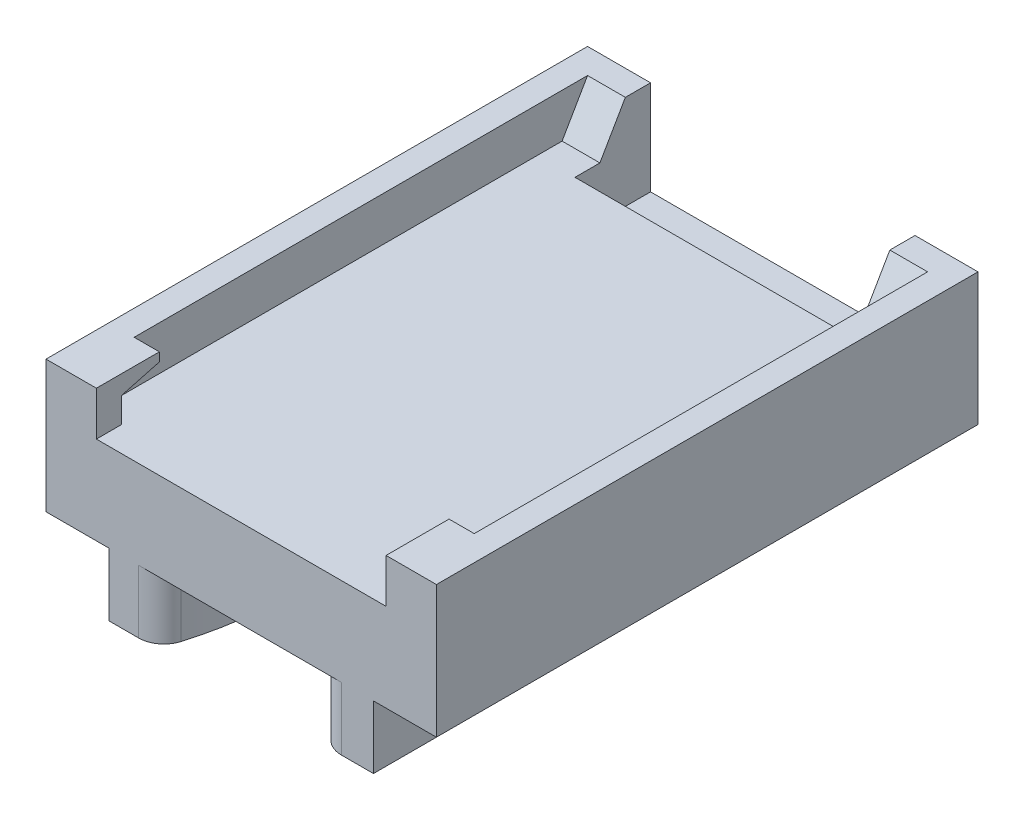
SolidWorks part; units mm, degrees
ref_plane "Płaszczyzna przednia" through (0, 0, 0) normal (0, 0, 1) x (1, 0, 0)
ref_plane "Płaszczyzna górna" through (0, 0, 0) normal (0, 1, 0) x (1, 0, 0)
ref_plane "Płaszczyzna prawa" through (0, 0, 0) normal (1, 0, 0) x (0, 0, -1)
sketch "Szkic1" plane through (0, 0, 0) normal (0, 1, 0) x (1, 0, 0)
  line L1 (-15.5, -21.5) -> (15.5, -21.5)
  line L2 (-15.5, -21.5) -> (-15.5, 21.5)
  line L3 (-15.5, 21.5) -> (15.5, 21.5)
  line L4 (15.5, -21.5) -> (15.5, 21.5)
  line L5 (-15.5, -21.5) -> (15.5, 21.5) construction
  line L6 (-15.5, 21.5) -> (15.5, -21.5) construction
  point P0 (0, 0)
  dimension "D1" = 31
  dimension "D2" = 43
extrude "Dodanie-wyciągnięcie1" add sketch "Szkic1" along normal blind 12
sketch "Szkic3" plane through (0, 0, 0) normal (0, -1, 0) x (1, 0, 0)
  line L19 (-10.2123, 28.1123) -> (-14.1254, 33.4595)
  line L21 (-10.2791, 46.0939) -> (-15.166, 51.1544)
  line L23 (-8.0445, 58.0315) -> (-4.2245, 54.0758)
  line L25 (5.1078, 53.9128) -> (9.0636, 57.7328)
  line L27 (15.9406, 50.6112) -> (10.88, 45.7243)
  line L29 (4.5535, 10.4212) -> (7.1435, -58.109)
  line L31 (6.5359, -61.1346) -> (1.3149, -72.3946)
  line L33 (-3.1199, -71.9285) -> (-5.8858, -59.8291)
  line L35 (-6.0512, -58.271) -> (-5.1193, 12.1724)
  arc A41 (-5.1193, 12.1724) -> (-10.2123, 28.1123) centre (-31.517, 12.5216) ccw
  arc A43 (-12.7415, 37.3422) -> (-14.1254, 33.4595) centre (-12.1147, 34.9308) ccw
  arc A45 (-12.7415, 37.3422) -> (-10.2791, 46.0939) centre (-14.0658, 42.4371) ccw
  arc A47 (-15.7507, 53.061) -> (-15.166, 51.1544) centre (-13.5835, 52.6827) ccw
  arc A49 (-10.429, 58.552) -> (-15.7507, 53.061) centre (-7.0711, 49.9733) ccw
  arc A51 (-8.0445, 58.0315) -> (-10.429, 58.552) centre (-9.6271, 56.5033) ccw
  arc A53 (-4.2245, 54.0758) -> (5.1078, 53.9128) centre (0.5231, 58.6605) ccw
  arc A55 (10.9702, 58.3174) -> (9.0636, 57.7328) centre (10.5918, 56.1502) ccw
  arc A57 (14.1036, 56.4511) -> (10.9702, 58.3174) centre (8.485, 50.5815) ccw
  arc A59 (16.4611, 52.9956) -> (14.1036, 56.4511) centre (7.7554, 49.5882) ccw
  arc A61 (15.9406, 50.6112) -> (16.4611, 52.9956) centre (14.4124, 52.1938) ccw
  arc A63 (10.88, 45.7243) -> (10.8712, 38.1593) centre (14.5367, 41.9376) ccw
  arc A65 (10.8712, 38.1593) -> (12.249, 37.1965) centre (14.5366, 41.9375) ccw
  arc A67 (13.9716, 36.3736) -> (12.249, 37.1965) centre (10.996, 32.3591) ccw
  arc A69 (14.2827, 32.9633) -> (13.9716, 36.3736) centre (12.3247, 34.504) ccw
  arc A71 (14.2827, 32.9633) -> (5.8286, 19.5982) centre (47.6073, 2.5276) ccw
  arc A73 (5.8286, 19.5982) -> (4.5535, 10.4212) centre (31.0167, 11.4214) ccw
  arc A75 (6.5359, -61.1346) -> (7.1435, -58.109) centre (0.5482, -58.3583) ccw
  arc A77 (-3.1199, -71.9285) -> (1.3149, -72.3946) centre (-0.8228, -71.4034) ccw
  arc A79 (-6.0512, -58.271) -> (-5.8858, -59.8291) centre (0.5482, -58.3583) ccw
extrude "Dodanie-wyciągnięcie3" add sketch "Szkic3" against normal offset from surface (5 mm away) 7 separate body up to face at (0, 12, 0)
combine bodies "Połącz1" operation type subtract main body 101 bodies to subtract 103
sketch "Szkic4" plane through (0, 0, 0) normal (0, -1, 0) x (1, 0, 0)
  line L0 (10.5, -21.5) -> (10.5, 21.5)
  line L2 (15.5, 21.5) -> (15.5, -21.5)
  line L3 (15.5, -21.5) -> (10.5, -21.5)
  line L4 (15.5, -21.5) -> (5.7599, -21.5) construction
  line L5 (6.6572, 21.5) -> (15.5, 21.5) construction
  line L6 (10.5, 21.5) -> (15.5, 21.5)
  line L7 (-15.5, -21.5) -> (-10.5, -21.5)
  line L8 (-5.5648, -21.5) -> (-15.5, -21.5) construction
  line L9 (-10.5, -21.5) -> (-10.5, 21.5)
  line L10 (-15.5, 21.5) -> (-6.6907, 21.5) construction
  line L11 (-10.5, 21.5) -> (-15.5, 21.5)
  line L12 (-15.5, 21.5) -> (-15.5, -21.5)
  dimension "D1" = 5
  dimension "D2" = 5
extrude "Wytnij-wyciągnięcie1" cut sketch "Szkic4" against normal up to surface (5 mm away) up to face at (0.7758, 5, 6.0462)
sketch "Szkic5" plane through (0, 12, 0) normal (0, 1, 0) x (1, 0, 0)
  line L0 (10.5, 19.5) -> (10.5, 21.5)
  line L1 (15.5, 21.5) -> (10.5, 21.5)
  line L2 (15.5, 21.5) -> (15.5, -21.5)
  line L3 (15.5, -21.5) -> (11.5, -21.5)
  line L4 (-15.5, 21.5) -> (-15.5, -21.5)
  line L5 (-13.5, -19.5) -> (-11.5, -19.5)
  line L6 (-13.5, -19.5) -> (-13.5, 19.5)
  line L7 (-13.5, 19.5) -> (-10.5, 19.5)
  line L8 (13.5, -19.5) -> (13.5, 19.5)
  line L9 (-13.5, -19.5) -> (13.5, 19.5) construction
  line L10 (-13.5, 19.5) -> (13.5, -19.5) construction
  line L11 (-10.5, 19.5) -> (-10.5, 21.5)
  line L12 (-10.5, 21.5) -> (-15.5, 21.5)
  line L13 (10.5, 19.5) -> (13.5, 19.5)
  line L14 (-11.5, -19.5) -> (-11.5, -21.5)
  line L15 (11.5, -19.5) -> (11.5, -21.5)
  line L16 (-11.5, -19.5) -> (11.5, -19.5) construction
  line L17 (11.5, -19.5) -> (13.5, -19.5)
  line L18 (11.5, -21.5) -> (-11.5, -21.5) construction
  line L19 (-11.5, -21.5) -> (-15.5, -21.5)
  point P6 (0, 0)
  dimension "D1" = 2
  dimension "D2" = 2
  dimension "D3" = 5
  dimension "D4" = 5
  dimension "D5" = 4
  dimension "D6" = 4
extrude "Dodanie-wyciągnięcie4" add sketch "Szkic5" along normal blind 3.5
sketch "Szkic6" plane through (0, 12, 0) normal (0, 1, 0) x (1, 0, 0)
  line L0 (10.5, 21.5) -> (10.5, 19.5) construction
  line L5 (-10.5, 21.5) -> (10.5, 21.5)
  line L6 (-10.5, 21.5) -> (-10.5, 15.5)
  line L7 (-10.5, 15.5) -> (10.5, 15.5)
  line L8 (10.5, 21.5) -> (10.5, 15.5)
  dimension "D1" = 6
extrude "Wytnij-wyciągnięcie2" cut sketch "Szkic6" against normal blind 4
chamfer "Sfazowanie1" distance 4 angle 40 1 edges at (0, 8, -15.5) first distance on face at (0, 10, -15.5)
chamfer "Sfazowanie2" distance 3.5 angle 30 2 edges at (12, 12, -19.5) (-12, 12, -19.5) first distance on face at (12, 13.75, -19.5) first distance on face at (-12, 13.75, -19.5)
fillet "Zaokrąglenie2" radius 2 2 edges at (6.6572, 2.5, 21.5) (-6.6907, 2.5, 21.5)
sketch "Szkic7" plane through (0, 0, 19.5) normal (0, 0, -1) x (-1, 0, 0)
  line L0 (11.5, 15.5) -> (13.5, 15.5) construction
  line L1 (11.5, 15.5) -> (13.5, 15.5)
  line L2 (11.5, 15.5) -> (11.5, 14)
  line L3 (11.5, 14) -> (13.5, 14)
  line L4 (13.5, 15.5) -> (13.5, 14)
  line L5 (13.5, 15.5) -> (13.5, 12) construction
  line L6 (-13.5, 15.5) -> (-13.5, 12) construction
  line L7 (-11.5, 15.5) -> (-13.5, 15.5)
  line L8 (-11.5, 15.5) -> (-11.5, 14)
  line L9 (-11.5, 14) -> (-13.5, 14)
  line L10 (-13.5, 15.5) -> (-13.5, 14)
  line L11 (11.5, 15.5) -> (11.5, 12) construction
  point P15 (11.5, 15.5)
  dimension "D1" = 1.5
  dimension "D2" = 1.5
extrude "Dodanie-wyciągnięcie5" add sketch "Szkic7" along normal blind 3
chamfer "Sfazowanie3" distance 3 angle 15 2 edges at (-12.5, 14, 16.5) (12.5, 14, 16.5) first distance on face at (-12.5, 14, 18) first distance on face at (12.5, 14, 18)
